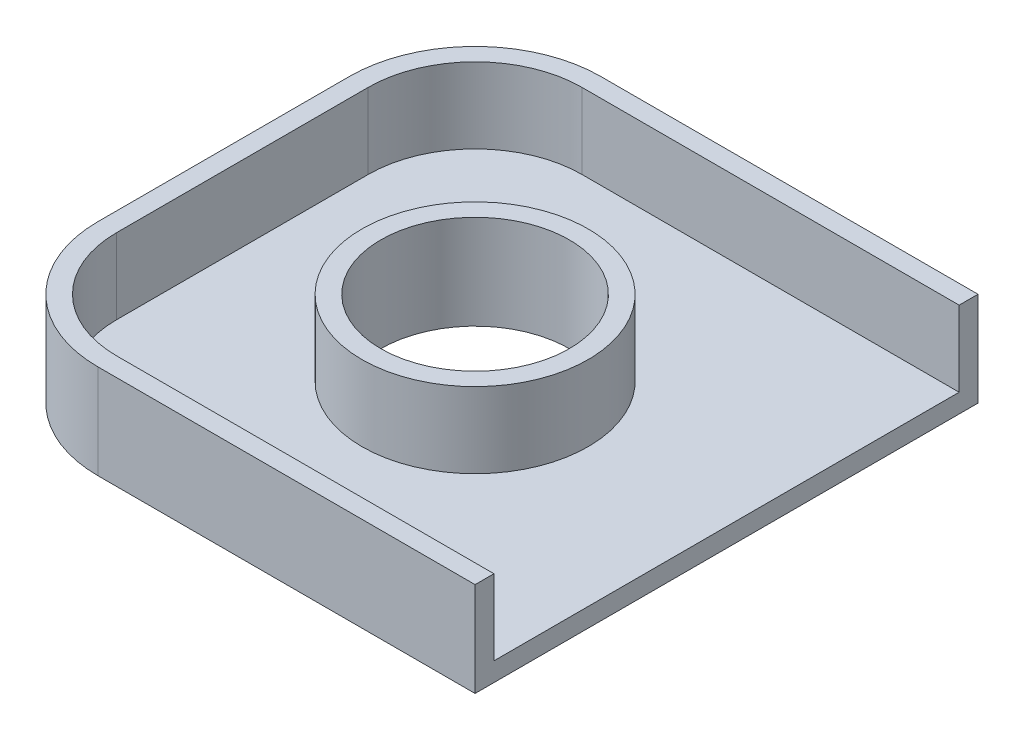
SolidWorks part; units mm, degrees
ref_plane "정면" through (0, 0, 0) normal (0, 0, 1) x (1, 0, 0)
ref_plane "윗면" through (0, 0, 0) normal (0, 1, 0) x (1, 0, 0)
ref_plane "우측면" through (0, 0, 0) normal (1, 0, 0) x (0, 0, -1)
sketch "스케치1" plane through (0, 0, 0) normal (0, 1, 0) x (1, 0, 0)
  line L0 (0, 0) -> (80, 0)
  line L1 (80, 0) -> (80, 80)
  line L2 (80, 80) -> (0, 80)
  line L3 (0, 80) -> (0, 0)
  line L4 (40, 80) -> (40, 0) construction
  line L5 (80, 40) -> (-13.6836, 40) construction
  dimension "D1" = 80
  dimension "D2" = 80
extrude "보스-돌출1" add sketch "스케치1" along normal blind 15 contours L2 L3 L0 L1
fillet "필렛1" radius 20 2 edges at (0, 7.5, -80) (0, 7.5, 0)
shell "쉘1" thickness 3 removed face at (80, 7.5, -40) removed face at (31.9526, 15, -40)
sketch "스케치2" plane through (0, 3, 0) normal (0, 1, 0) x (1, 0, 0)
  line L0 (80, 3) -> (80, 77) construction
  circle A0 centre (40, 40) radius 18
  circle A1 centre (40, 40) radius 15
  dimension "D1" = 40
extrude "보스-돌출2" add sketch "스케치2" along normal blind 12 contours A0
extrude "컷-돌출1" cut sketch "스케치2<3>" against normal blind 15 and the other way blind 15 contours A1
sketch "스케치2<3>" plane through (0, 3, 0) normal (0, 1, 0) x (1, 0, 0) same geometry as "스케치2"
